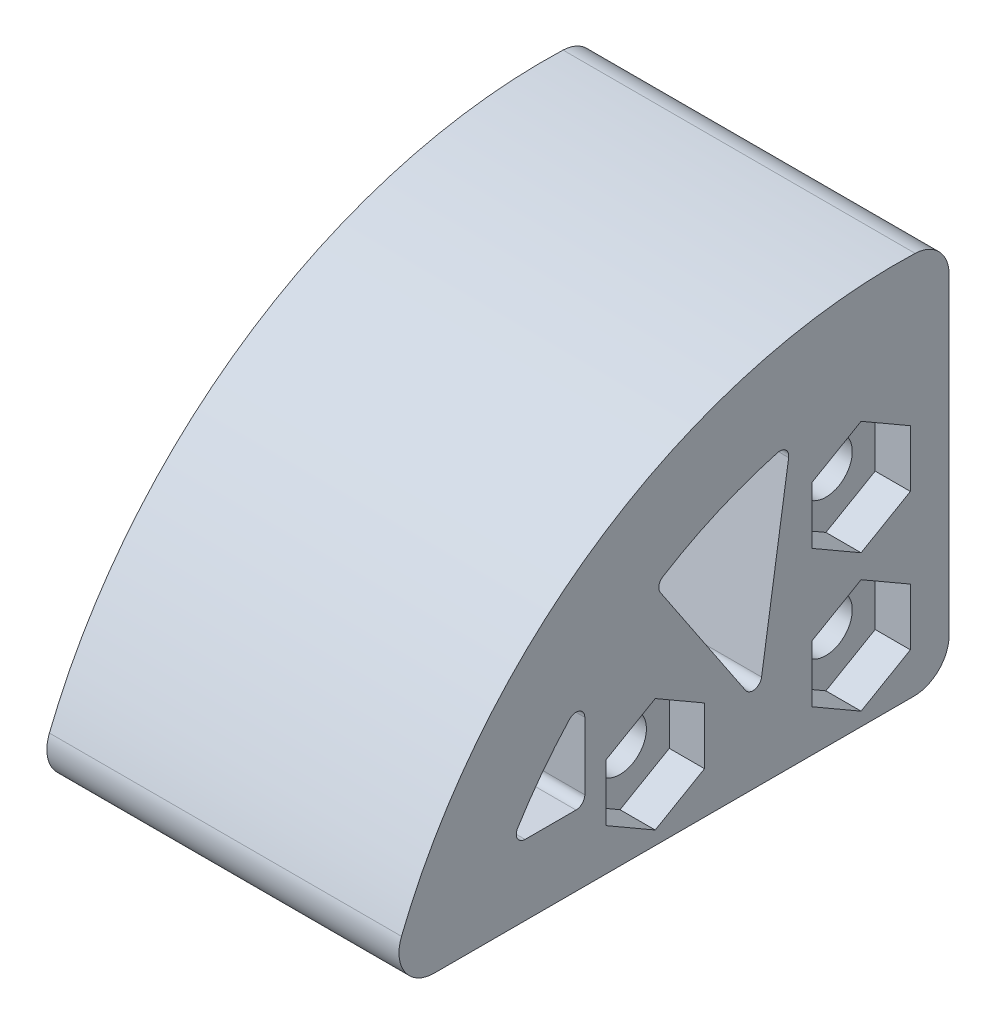
SolidWorks part; units mm, degrees
ref_plane "Front Plane" through (0, 0, 0) normal (0, 0, 1) x (1, 0, 0)
ref_plane "Top Plane" through (0, 0, 0) normal (0, 1, 0) x (1, 0, 0)
ref_plane "Right Plane" through (0, 0, 0) normal (1, 0, 0) x (0, 0, -1)
sketch "Sketch1" plane through (0, 0, 0) normal (1, 0, 0) x (0, 0, -1)
  line L0 (0, 0) -> (0, 7.7921) construction
  line L1 (0, 7.7921) -> (-11.6942, 0) construction
  line L2 (-11.6942, 0) -> (0, 0) construction
  line L3 (-24.25, -4) -> (3, -4)
  line L4 (5, -2) -> (5, 15.7544)
  line L5 (-16.1942, 0) -> (-19.0869, 0)
  line L6 (-22.5147, 0) -> (17, 0) construction
  line L7 (-15.6942, 0.5) -> (-15.6942, 4.3116)
  line L9 (-11.4085, 8.3132) -> (-6.5621, 1.0687)
  line L11 (-5.6523, 1.271) -> (-4.1151, 11.2984)
  line L12 (-11.6942, 0) -> (-11.6942, 13.3375) construction
  line L15 (0, 15.0021) -> (0, -9) construction
  circle A0 centre (0, 7.7921) radius 1.5
  circle A1 centre (0, 0) radius 1.5
  circle A2 centre (-11.6942, 0) radius 1.5
  arc A3 (3.0707, 17.7532) -> (-26.107, -1.2572) centre (2, -12.5) ccw
  arc A4 (-26.107, -1.2572) -> (-24.25, -4) centre (-24.25, -2) ccw
  arc A5 (3, -4) -> (5, -2) centre (3, -2) ccw
  arc A6 (5, 15.7544) -> (3.0707, 17.7532) centre (3, 15.7544) ccw
  arc A7 (-19.5125, 0.7624) -> (-16.5614, 4.6509) centre (2, -12.5) cw
  arc A8 (-11.2552, 9.017) -> (-4.7428, 11.856) centre (2, -12.5) cw
  arc A9 (-6.5621, 1.0687) -> (-5.6523, 1.271) centre (-6.1465, 1.3468) ccw
  arc A10 (-16.1942, 0) -> (-15.6942, 0.5) centre (-16.1942, 0.5) ccw
  arc A11 (-19.0869, 0) -> (-19.5125, 0.7624) centre (-19.0869, 0.5) cw
  arc A12 (-15.6942, 4.3116) -> (-16.5614, 4.6509) centre (-16.1942, 4.3116) ccw
  arc A13 (-11.4085, 8.3132) -> (-11.2552, 9.017) centre (-10.9929, 8.5913) cw
  arc A14 (-4.7428, 11.856) -> (-4.1151, 11.2984) centre (-4.6094, 11.3741) cw
  point P16 (-5.8471, 0)
  point P48 (-5.8471, 0)
  point P51 (-15.6942, 0)
  point P54 (-19.9643, 0)
  point P59 (-11.6942, 8.7403)
  point P62 (-4, 12.0495)
  dimension "D1" = 3
  dimension "D2" = 2
  dimension "D5" = 5
  dimension "D10" = 5
  dimension "D12" = 0.5
  dimension "D3" = 4
  dimension "D4" = 5
  dimension "D6" = 3
  dimension "D7" = 4
  dimension "D8" = 8.5
  dimension "D9" = 27.25
  dimension "D11" = 4
extrude "Boss-Extrude1" add sketch "Sketch1" along normal blind 20
sketch "Sketch2" plane through (0, 0, 0) normal (1, 0, 0) x (0, 0, -1)
  line L1 (-11.6942, -3.2332) -> (-8.8942, -1.6166)
  line L2 (-8.8942, -1.6166) -> (-8.8942, 1.6166)
  line L3 (-8.8942, 1.6166) -> (-11.6942, 3.2332)
  line L4 (-11.6942, 3.2332) -> (-14.4942, 1.6166)
  line L5 (-14.4942, 1.6166) -> (-14.4942, -1.6166)
  line L6 (-14.4942, -1.6166) -> (-11.6942, -3.2332)
  line L7 (0, -3.2332) -> (2.8, -1.6166)
  line L8 (2.8, -1.6166) -> (2.8, 1.6166)
  line L9 (2.8, 1.6166) -> (0, 3.2332)
  line L10 (0, 3.2332) -> (-2.8, 1.6166)
  line L11 (-2.8, 1.6166) -> (-2.8, -1.6166)
  line L12 (-2.8, -1.6166) -> (0, -3.2332)
  line L13 (0, 4.5589) -> (2.8, 6.1755)
  line L14 (2.8, 6.1755) -> (2.8, 9.4087)
  line L15 (2.8, 9.4087) -> (0, 11.0253)
  line L16 (0, 11.0253) -> (-2.8, 9.4087)
  line L17 (-2.8, 9.4087) -> (-2.8, 6.1755)
  line L18 (-2.8, 6.1755) -> (0, 4.5589)
  circle A0 centre (-11.6942, 0) radius 2.8 construction
  circle A1 centre (0, 0) radius 2.8 construction
  circle A2 centre (0, 7.7921) radius 2.8 construction
  dimension "D1" = 5.6
  dimension "D2" = 5.6
  dimension "D3" = 5.6
extrude "Cut-Extrude1" cut sketch "Sketch2" along normal blind 2 from surface starting at face at (0, 7.1577, 7.2942)
extrude "Cut-Extrude2" cut sketch "Sketch2<2>" against normal blind 2 from surface starting at face at (20, 0, -1.5)
sketch "Sketch2<2>" plane through (0, 0, 0) normal (1, 0, 0) x (0, 0, -1) same geometry as "Sketch2"
